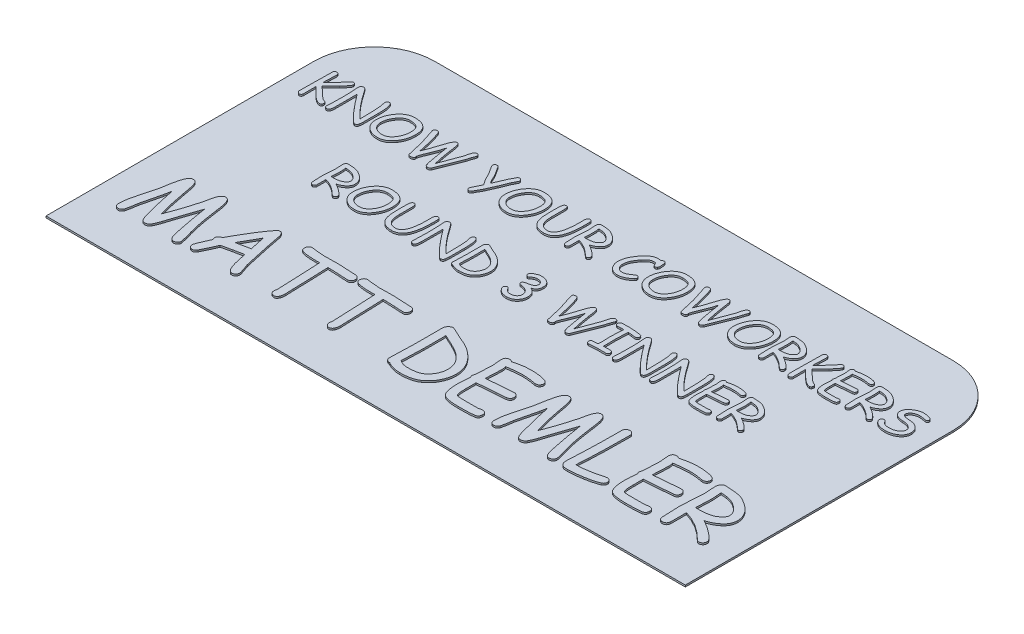
SolidWorks part; units mm, degrees
ref_plane "Front Plane" through (0, 0, 0) normal (0, 0, 1) x (1, 0, 0)
ref_plane "Top Plane" through (0, 0, 0) normal (0, 1, 0) x (1, 0, 0)
ref_plane "Right Plane" through (0, 0, 0) normal (1, 0, 0) x (0, 0, -1)
sketch "Sketch1" plane through (0, 0, 0) normal (0, 1, 0) x (1, 0, 0)
  line L1 (37, -19) -> (-37, -19)
  line L2 (37, -19) -> (37, 19)
  line L3 (37, 19) -> (-37, 19)
  line L4 (-37, -19) -> (-37, 19)
  line L5 (37, -19) -> (-37, 19) construction
  line L6 (37, 19) -> (-37, -19) construction
  point P0 (0, 0)
  dimension "D1" = 74
  dimension "D2" = 38
extrude "Boss-Extrude1" add sketch "Sketch1" along normal blind 0.2
fillet "Fillet2" radius 7 2 edges at (37, 0.1, -19) (-37, 0.1, -19)
sketch "Sketch2" plane through (0, 0.2, 0) normal (0, 1, 0) x (1, 0, 0)
  line L0 (-37, 8) -> (37, 8) construction
  line L1 (-37, 12) -> (-37, -19) construction
  line L3 (-37, -14) -> (37, -14) construction
  line L4 (37, -19) -> (37, 12) construction
  text T0 "KNOW YOUR COWORKERS\r\nROUND 3 WINNER" font "Comic Sans MS" height 4
  text T1 "MATT DEMLER" font "Comic Sans MS" height 7
  point P4 (37, -14)
  point P11 (0, 0)
  point P12 (0, 0)
  point P13 (36.125, -14)
  point P14 (33.9188, -14)
  point P15 (35.1382, -14)
  point P16 (0, 0)
  point P17 (36.1212, -14)
  point P18 (0, 0)
  point P19 (35.733, -14)
  point P20 (0, 0)
  point P21 (30.2528, 8)
  point P22 (0, 0)
  point P23 (0, 0)
  point P24 (0, 0)
  dimension "D1" = 8
  dimension "D2" = 14
extrude "Boss-Extrude3" add sketch "Sketch2" along normal blind 0.2
